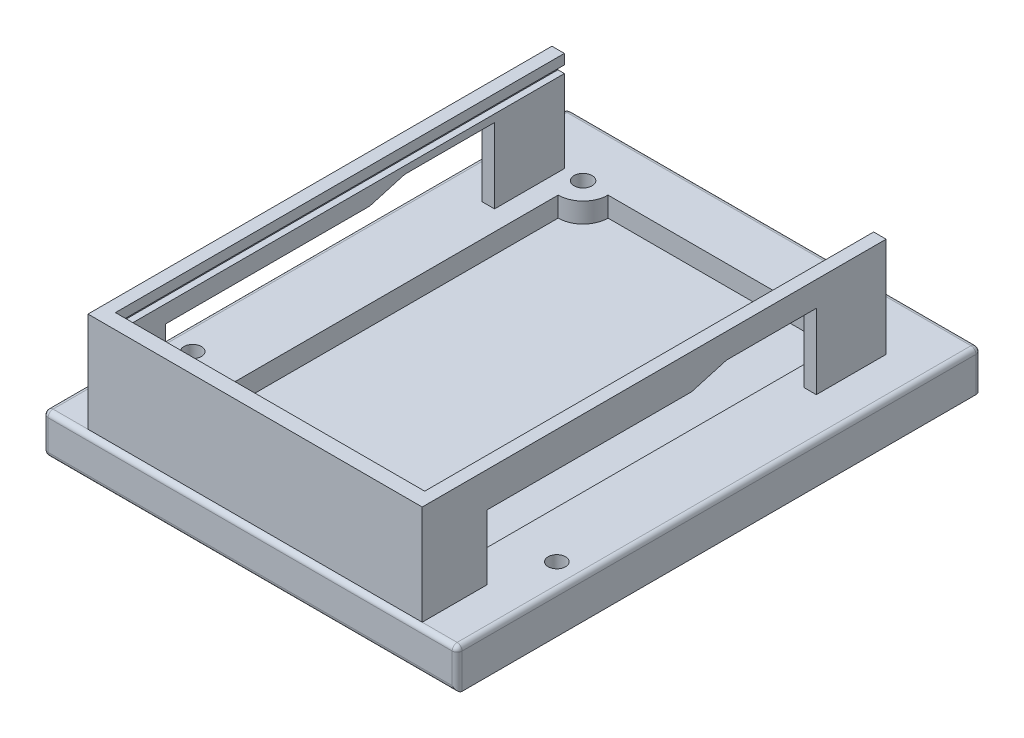
SolidWorks part; units mm, degrees
ref_plane "Front Plane" through (0, 0, 0) normal (0, 0, 1) x (1, 0, 0)
ref_plane "Top Plane" through (0, 0, 0) normal (0, 1, 0) x (1, 0, 0)
ref_plane "Right Plane" through (0, 0, 0) normal (1, 0, 0) x (0, 0, -1)
sketch "Sketch1" plane through (0, 0, 0) normal (0, 1, 0) x (1, 0, 0)
  line L0 (41.5, 95) -> (41.5, 0) construction
  line L1 (0, 0) -> (83, 0)
  line L2 (0, 0) -> (0, 105)
  line L3 (0, 105) -> (83, 105)
  line L4 (83, 0) -> (83, 105)
  line L5 (14.475, 93.775) -> (14.475, 11.225) construction
  circle A0 centre (5, 25) radius 1.75
  circle A1 centre (14.475, 11.225) radius 1.65 construction
  circle A2 centre (14.475, 93.775) radius 1.65 construction
  circle A3 centre (78, 25) radius 1.75
  circle A4 centre (68.525, 11.225) radius 1.65 construction
  circle A5 centre (68.525, 93.775) radius 1.65 construction
  point P19 (14.475, 52.5)
  point P20 (41.5, 0)
  point P21 (0, 52.5)
  dimension "D2" = 36.5
  dimension "D3" = 3.5
  dimension "D5" = 13.775
  dimension "D6" = 27.025
  dimension "D7" = 3.3
  dimension "D9" = 82.55
  dimension "D10" = 3.3
  dimension "D1" = 83
  dimension "D4" = 105
extrude "Boss-Extrude1" add sketch "Sketch1" along normal blind 8
sketch "Sketch3" plane through (0, 0, 0) normal (0, -1, 0) x (1, 0, 0)
  point P0 (14.475, -11.225)
  point P1 (68.525, -11.225)
  point P3 (68.525, -93.775)
  point P5 (14.475, -93.775)
hole_wizard "CBORE for M3 SHCS1" positions "Sketch3" profile "Sketch4" counterbore size "M3" standard "ANSI Metric" end condition through all
sketch "Sketch4" plane through (14.475, 0, -11.225) normal (1, 0, 0) x (0, 0, -1)
  line L0 (0, 0) -> (0, 8)
  line L1 (0, 8) -> (1.8, 8)
  line L3 (1.8, 8) -> (1.8, 3)
  line L4 (1.8, 3) -> (3.25, 3)
  line L5 (3.25, 3) -> (3.25, 0)
  line L7 (3.25, 0) -> (0, 0)
  line L11 (0, -6.35) -> (0, 107.95) construction
  dimension "Thru Hole Dia." = 3.6
  dimension "Thru Hole Depth" = 8
  dimension "C'Bore Dia." = 6.5
  dimension "C'Bore Depth" = 3
sketch "Sketch5" plane through (0, 8, 0) normal (0, 1, 0) x (1, 0, 0)
  line L1 (19.475, 93.775) -> (63.525, 93.775)
  line L2 (14.475, 88.775) -> (14.475, 16.225)
  line L3 (19.475, 11.225) -> (63.525, 11.225)
  line L4 (68.525, 88.775) -> (68.525, 16.225)
  line L5 (41.5, 200095) -> (41.5, -200000) construction
  circle A0 centre (14.475, 93.775) radius 1.65 construction
  circle A1 centre (14.475, 11.225) radius 1.65 construction
  arc A3 (14.475, 88.775) -> (19.475, 93.775) centre (14.475, 93.775) ccw
  arc A4 (63.525, 93.775) -> (68.525, 88.775) centre (68.525, 93.775) ccw
  arc A5 (68.525, 16.225) -> (63.525, 11.225) centre (68.525, 11.225) ccw
  arc A6 (19.475, 11.225) -> (14.475, 16.225) centre (14.475, 11.225) ccw
  dimension "D3" = 54.05
  dimension "D4" = 27.025
  dimension "D1" = 0
  dimension "D2" = 0
extrude "Cut-Extrude1" cut sketch "Sketch5" against normal blind 4
sketch "Sketch6" plane through (0, 0, 0) normal (0, -1, 0) x (1, 0, 0)
  line L1 (11.475, -35) -> (16.475, -35)
  line L2 (11.475, -35) -> (11.475, -55)
  line L3 (11.475, -55) -> (16.475, -55)
  line L4 (16.475, -35) -> (16.475, -55)
  dimension "D1" = 5
  dimension "D2" = 20
  dimension "D3" = 3
  dimension "D4" = 10
extrude "Boss-Extrude2" add sketch "Sketch6" along normal blind 8.8
sketch "Sketch7" plane through (0, 0, -55) normal (0, 0, -1) x (-1, 0, 0)
  line L0 (-16.475, -8.8) -> (-16.475, 0) construction
  line L1 (-11.475, 0) -> (-14.675, 0)
  line L2 (-11.475, 0) -> (-11.475, -6.8)
  line L3 (-11.475, -6.8) -> (-14.675, -6.8)
  line L4 (-14.675, 0) -> (-14.675, -6.8)
  dimension "D1" = 6.8
  dimension "D2" = 1.8
extrude "Cut-Extrude2" cut sketch "Sketch7" against normal through all
fillet "Fillet1" radius 6 1 edges at (16.475, 0, -45) second distance 8 first distance on face at (14.475, 0, -14.475)
fillet "Fillet2" radius 1 10 edges at (0, 4, 0) (41.5, 8, 0) (83, 4, 0) (83, 4, -105) (83, 8, -52.5) (41.5, 8, -105) (0, 4, -105) (0, 8, -52.5) (0, 0, -52.5) (41.5, 0, 0)
sketch "Sketch8" plane through (0, 8, 0) normal (0, 1, 0) x (1, 0, 0)
  line L1 (8, 94) -> (75, 94)
  line L2 (8, 94) -> (8, 1)
  line L3 (8, 1) -> (75, 1)
  line L4 (75, 94) -> (75, 1)
  line L6 (1, 1) -> (82, 1) construction
  circle A4 centre (5, 25) radius 1.75 construction
  dimension "D1" = 3
  dimension "D3" = 93
  dimension "D2" = 3
  dimension "D4" = 0
extrude "Boss-Extrude4" add sketch "Sketch8" along normal blind 20
sketch "Sketch11" plane through (0, 0, -94) normal (0, 0, -1) x (-1, 0, 0)
  line L0 (-75, 8) -> (-70.3109, 8) construction
  line L1 (-72.5, 8) -> (-10.5, 8)
  line L2 (-72.5, 8) -> (-72.5, 24.5)
  line L3 (-72.5, 28) -> (-10.5, 28)
  line L4 (-10.5, 8) -> (-10.5, 24.5)
  line L5 (-75, 28) -> (-75, 8) construction
  line L6 (-8, 28) -> (-8, 8) construction
  line L7 (-75, 28) -> (-8, 28) construction
  line L8 (-10.5, 24.5) -> (-9.2, 24.5)
  line L9 (-73.8, 26) -> (-72.5, 26)
  line L10 (-73.8, 26) -> (-73.8, 24.5)
  line L11 (-73.8, 24.5) -> (-72.5, 24.5)
  line L12 (-9.2, 26) -> (-9.2, 24.5)
  line L13 (-10.5, 26) -> (-9.2, 26)
  line L14 (-72.5, 26) -> (-72.5, 28)
  line L15 (-10.5, 26) -> (-10.5, 28)
  dimension "D1" = 2.5
  dimension "D2" = 2.5
  dimension "D3" = 0
  dimension "D4" = 1.2
  dimension "D5" = 1.5
  dimension "D6" = 1.2
  dimension "D7" = 2
extrude "Cut-Extrude3" cut sketch "Sketch11" against normal blind 90
sketch "Sketch12" plane through (0, 0, -4) normal (0, 0, -1) x (-1, 0, 0)
  line L1 (-73.8, 26) -> (-9.2, 26)
  line L2 (-73.8, 26) -> (-73.8, 24.5)
  line L3 (-73.8, 24.5) -> (-9.2, 24.5)
  line L4 (-9.2, 26) -> (-9.2, 24.5)
extrude "Cut-Extrude4" cut sketch "Sketch12" against normal blind 1
sketch "Sketch15" plane through (75, 0, 0) normal (1, 0, 0) x (0, 0, -1)
  line L0 (1, 8) -> (104, 8) construction
  line L1 (55, 8) -> (37, 8)
  line L2 (55, 8) -> (55, 21) construction
  line L3 (55, 21) -> (37, 21)
  line L4 (37, 8) -> (37, 21) construction
  line L5 (32, 21) -> (37, 21)
  line L6 (1, 8) -> (94, 8) construction
  line L7 (32, 8) -> (14, 8)
  line L8 (32, 8) -> (32, 21) construction
  line L9 (32, 21) -> (14, 21)
  line L10 (14, 8) -> (14, 21)
  line L11 (1, 28) -> (1, 8) construction
  line L12 (32, 8) -> (37, 8)
  line L13 (55, 21) -> (62, 23)
  line L14 (62, 23) -> (80, 23)
  line L15 (62, 23) -> (62, 8) construction
  line L16 (62, 8) -> (80, 8)
  line L17 (80, 23) -> (80, 8)
  line L18 (55, 8) -> (62, 8)
  dimension "D1" = 18
  dimension "D2" = 13
  dimension "D3" = 13
  dimension "D4" = 18
  dimension "D5" = 13
  dimension "D6" = 5
  dimension "D7" = 18
  dimension "D8" = 15
  dimension "D9" = 7
extrude "Cut-Extrude5" cut sketch "Sketch15" against normal through all and the other way through all
